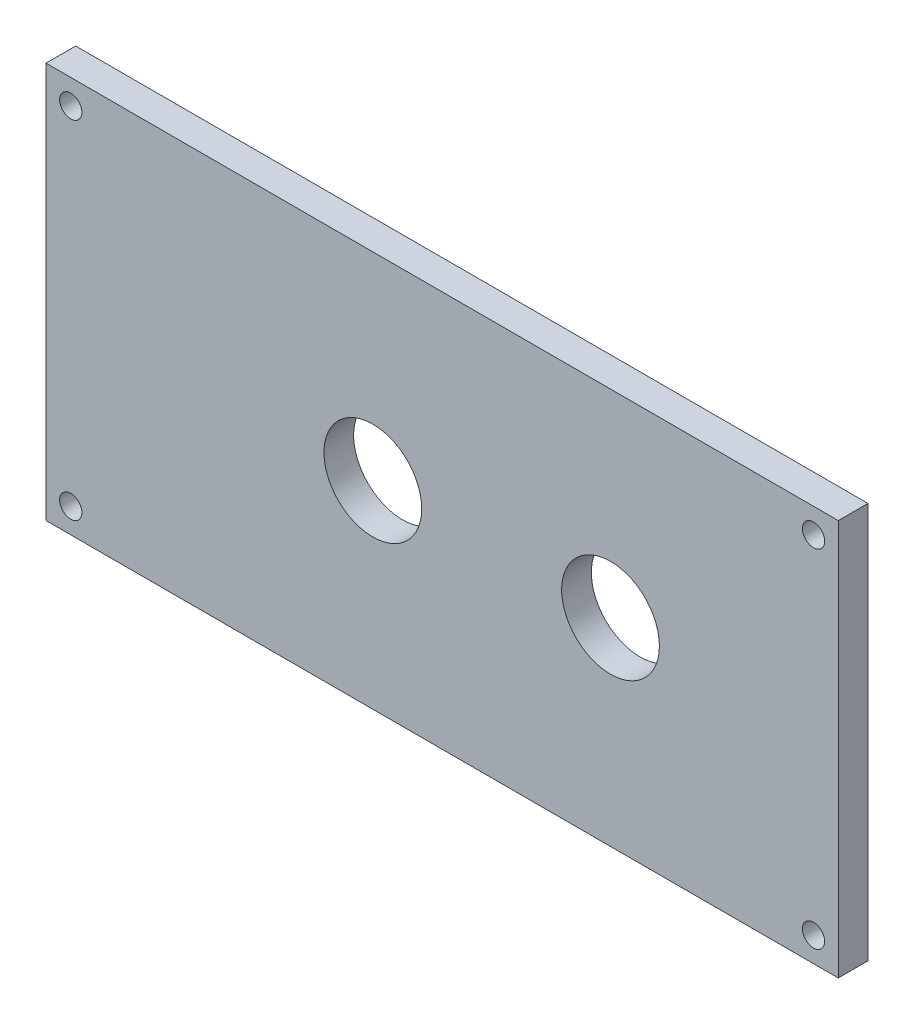
SolidWorks part; units mm, degrees
ref_plane "Front Plane" through (0, 0, 0) normal (0, 0, 1) x (1, 0, 0)
ref_plane "Top Plane" through (0, 0, 0) normal (0, 1, 0) x (1, 0, 0)
ref_plane "Right Plane" through (0, 0, 0) normal (1, 0, 0) x (0, 0, -1)
sketch "Sketch1" plane through (0, 0, 0) normal (0, 0, 1) x (1, 0, 0)
  line L1 (0, 0) -> (80, 0)
  line L2 (0, 0) -> (0, 40)
  line L3 (0, 40) -> (80, 40)
  line L4 (80, 0) -> (80, 40)
  dimension "D1" = 80
  dimension "D2" = 40
extrude "Boss-Extrude1" add sketch "Sketch1" along normal blind 3 contours L3 L4 L1 L2
sketch "Sketch2" plane through (0, 0, 3) normal (0, 0, 1) x (1, 0, 0)
  line L0 (0, 20) -> (80, 20) construction
  line L1 (0, 0) -> (0, 40) construction
  line L2 (80, 0) -> (80, 40) construction
  line L3 (0, 40) -> (80, 40) construction
  line L4 (40, 40) -> (40, 0) construction
  line L5 (0, 0) -> (80, 0) construction
  line L6 (48.175, 16) -> (48.175, 8)
  line L7 (45, 32) -> (48.175, 32)
  line L8 (45, 32) -> (45, 24)
  line L9 (45, 24) -> (48.175, 24)
  line L10 (48.175, 32) -> (48.175, 24)
  line L11 (45, 8) -> (48.175, 8)
  line L12 (45, 16) -> (45, 8)
  line L13 (45, 16) -> (48.175, 16)
  line L14 (48.175, 32) -> (48.175, 16) construction
  circle A1 centre (33, 20) radius 4.9365
  circle A2 centre (57, 20) radius 4.9365
  circle A3 centre (2.5, 37.5) radius 1.125
  circle A4 centre (77.5, 37.5) radius 1.125
  circle A5 centre (77.5, 2.5) radius 1.125
  circle A6 centre (2.5, 2.5) radius 1.125
  dimension "D1" = 33
  dimension "D2" = 9.873
  dimension "D3" = 9.873
  dimension "D7" = 2.25
  dimension "D4" = 3.175
  dimension "D5" = 8
  dimension "D6" = 24
  dimension "D8" = 2.5
  dimension "D9" = 2.5
  dimension "D10" = 12
  dimension "D11" = 16
  dimension "D13" = 16
  dimension "D12" = 2
extrude "Cut-Extrude1" cut sketch "Sketch2" against normal through all contours A3 | A6 | A1 | A2 | A4 | A5 region at (33, 20, 3) region at (57, 20, 3) region at (2.5, 37.5, 3) region at (77.5, 37.5, 3) region at (77.5, 2.5, 3) region at (2.5, 2.5, 3)
